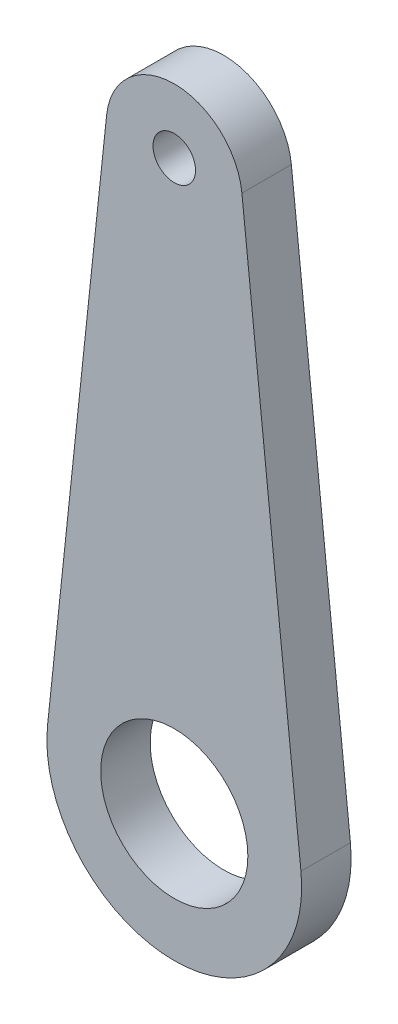
SolidWorks part; units mm, degrees
ref_plane "Front Plane" through (0, 0, 0) normal (0, 0, 1) x (1, 0, 0)
ref_plane "Top Plane" through (0, 0, 0) normal (0, 1, 0) x (1, 0, 0)
ref_plane "Right Plane" through (0, 0, 0) normal (1, 0, 0) x (0, 0, -1)
sketch "Sketch1" plane through (0, 0, 0) normal (0, 0, 1) x (1, 0, 0)
  line L0 (-6.5042, 0.6885) -> (-3.4731, 29.3236)
  line L1 (6.5042, 0.6885) -> (3.4731, 29.3236)
  arc A0 (-6.5042, 0.6885) -> (6.5042, 0.6885) centre (0, 0) ccw
  arc A1 (3.4731, 29.3236) -> (-3.4731, 29.3236) centre (0, 28.956) ccw
  circle A2 centre (0, 0) radius 3.7782
  circle A3 centre (0, 29.1465) radius 1.0922
  dimension "D2" = 38.989
  dimension "D3" = 6.985
  dimension "D1" = 13.081
  dimension "D4" = 7.5565
  dimension "D5" = 34.5948
  dimension "D6" = 2.1844
extrude "Boss-Extrude1" add sketch "Sketch1" along normal blind 2.54
ref_axis "Axis1" through (0, 0, 2.54) along (0, 0, -1)
ref_axis "Axis2" through (0, 29.1465, 2.54) along (0, 0, -1)
